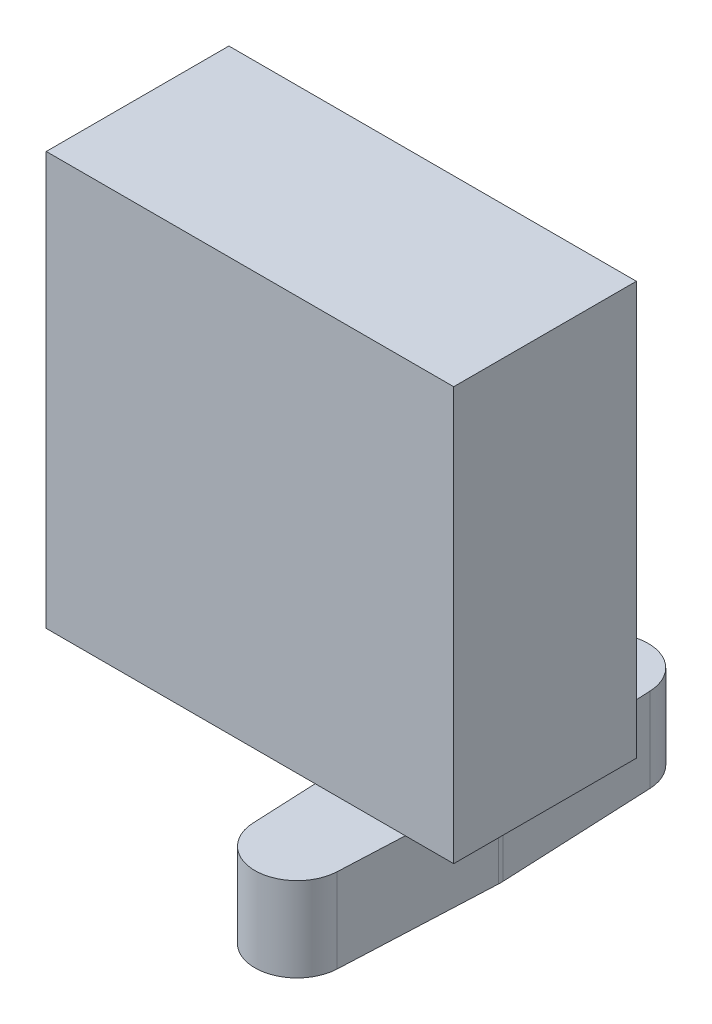
SolidWorks part; units mm, degrees
ref_plane "XY" through (0, 0, 0) normal (0, 0, 1) x (1, 0, 0)
ref_plane "XZ" through (0, 0, 0) normal (0, 1, 0) x (1, 0, 0)
ref_plane "YZ" through (0, 0, 0) normal (1, 0, 0) x (0, 0, -1)
ref_axis "X" through (-19.4325, 0, 0) along (1, 0, 0)
ref_axis "Y" through (0, -16.17, 0) along (0, 1, 0)
ref_axis "Z" through (0, 0, 12.1) along (0, 0, -1)
sketch "Sketch1" plane through (0, 0, 0) normal (0, 0, 1) x (1, 0, 0)
  line L1 (-14.5, -14.7) -> (14.5, -14.7)
  line L2 (-14.5, -14.7) -> (-14.5, 14.7)
  line L3 (-14.5, 14.7) -> (14.5, 14.7)
  line L4 (14.5, -14.7) -> (14.5, 14.7)
  line L5 (-14.5, -14.7) -> (14.5, 14.7) construction
  line L6 (-14.5, 14.7) -> (14.5, -14.7) construction
  point P0 (0, 0)
  dimension "D1" = 29.4
  dimension "D2" = 29
extrude "Boss-Extrude1" add sketch "Sketch1" along normal mid plane 13
sketch "Sketch3" plane through (0, -14.7, 0) normal (0, -1, 0) x (1, 0, 0)
  line L0 (4.3536, -0.1591) -> (4.8531, -11.1364)
  line L1 (10.8469, -11.1364) -> (11.3464, -0.1591)
  line L2 (11.3464, 0.1591) -> (10.8469, 11.1364)
  line L3 (4.8531, 11.1364) -> (4.3536, 0.1591)
  line L4 (7.85, -11) -> (7.85, 11) construction
  line L5 (11.35, 0) -> (4.35, 0) construction
  line L6 (0, 0) -> (7.85, 0) construction
  line L7 (17.65, 0) -> (-17.65, 0) construction
  arc A1 (4.8531, -11.1364) -> (10.8469, -11.1364) centre (7.85, -11) ccw
  arc A2 (10.8469, 11.1364) -> (4.8531, 11.1364) centre (7.85, 11) ccw
  arc A3 (4.3536, 0.1591) -> (4.3536, -0.1591) centre (7.85, 0) ccw
  arc A4 (11.3464, -0.1591) -> (11.3464, 0.1591) centre (7.85, 0) ccw
  circle A5 centre (7.85, 0) radius 11 construction
  point P14 (7.3577, -14.138)
  point P19 (0, 0)
  point P20 (0, 0)
  point P21 (-5.8881, -8.1422)
  point P22 (0, 0)
  point P23 (7.6338, 0)
  point P24 (15.3803, -6.6786)
  point P25 (14.564, -6.3899)
  point P26 (8.606, -10.551)
  dimension "D2" = 11
  dimension "D3" = 3.5
  dimension "D1" = 3
  dimension "D4" = 35.3
  dimension "D5" = 9.8
extrude "Boss-Extrude2" add sketch "Sketch3" along normal blind 6 separate body contours L3 A3 L0 A1 L1 A4 L2 A2
